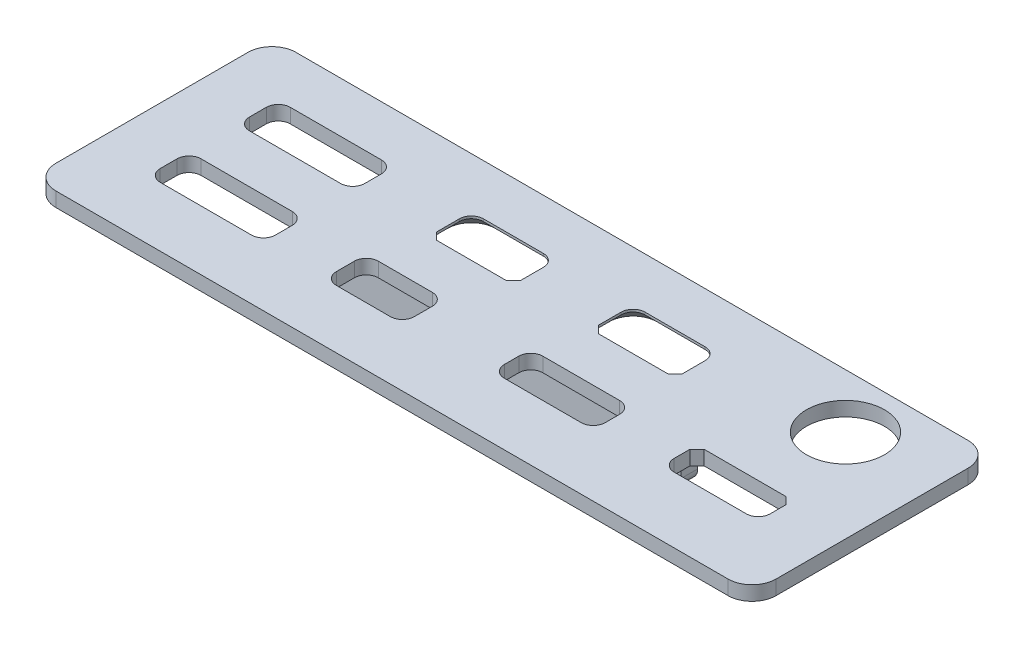
SolidWorks part; units mm, degrees
ref_plane "前视基准面" through (0, 0, 0) normal (0, 0, 1) x (1, 0, 0)
ref_plane "上视基准面" through (0, 0, 0) normal (0, 1, 0) x (1, 0, 0)
ref_plane "右视基准面" through (0, 0, 0) normal (1, 0, 0) x (0, 0, -1)
sketch "草图1" plane through (0, 0, 0) normal (0, 1, 0) x (1, 0, 0)
  line L1 (-30, 10) -> (30, 10)
  line L2 (-30, 10) -> (-30, -10)
  line L3 (-30, -10) -> (30, -10)
  line L4 (30, 10) -> (30, -10)
  line L5 (-30, 10) -> (30, -10) construction
  line L6 (-30, -10) -> (30, 10) construction
  point P0 (0, 0)
  dimension "D1" = 60
  dimension "D2" = 20
extrude "凸台-拉伸1" add sketch "草图1" along normal blind 1.2
fillet "圆角1" radius 2 4 edges at (30, 0.6, 10) (30, 0.6, -10) (-30, 0.6, 10) (-30, 0.6, -10)
sketch "草图4" plane through (0, 1.2, 0) normal (0, 1, 0) x (1, 0, 0)
  line L0 (-30, 8) -> (-30, -8) construction
  line L1 (-25.2717, 5.8) -> (-15.6717, 5.8)
  line L2 (-25.2717, 5.8) -> (-25.2717, 2.4)
  line L3 (-25.2717, 2.4) -> (-15.6717, 2.4)
  line L4 (-15.6717, 5.8) -> (-15.6717, 2.4)
  line L5 (-9.1829, 5.8) -> (-2.1829, 5.8)
  line L6 (-9.1829, 5.8) -> (-9.1829, 2.3)
  line L7 (-9.1829, 2.3) -> (-2.1829, 2.3)
  line L8 (-2.1829, 5.8) -> (-2.1829, 2.3)
  line L9 (4.2885, 5.8) -> (11.2885, 5.8)
  line L10 (4.2885, 5.8) -> (4.2885, 2.3)
  line L11 (4.2885, 2.3) -> (11.2885, 2.3)
  line L12 (11.2885, 5.8) -> (11.2885, 2.3)
  line L13 (17.05, -1.6348) -> (25.05, -1.6348)
  line L14 (17.05, -1.6348) -> (17.05, -4.5348)
  line L15 (17.05, -4.5348) -> (25.05, -4.5348)
  line L16 (25.05, -1.6348) -> (25.05, -4.5348)
  line L17 (3.2, -1.6348) -> (11.6, -1.6348)
  line L18 (3.2, -1.6348) -> (3.2, -4.8348)
  line L19 (3.2, -4.8348) -> (11.6, -4.8348)
  line L20 (11.6, -1.6348) -> (11.6, -4.8348)
  line L21 (-10.5, -1.6348) -> (-4, -1.6348)
  line L22 (-10.5, -1.6348) -> (-10.5, -5.1348)
  line L23 (-10.5, -5.1348) -> (-4, -5.1348)
  line L24 (-4, -1.6348) -> (-4, -5.1348)
  line L25 (-25.2717, -1.6348) -> (-15.6717, -1.6348)
  line L26 (-25.2717, -1.6348) -> (-25.2717, -5.0348)
  line L27 (-25.2717, -5.0348) -> (-15.6717, -5.0348)
  line L28 (-15.6717, -1.6348) -> (-15.6717, -5.0348)
  line L29 (28, 10) -> (-28, 10) construction
  line L30 (-28, -10) -> (28, -10) construction
  line L31 (30, -8) -> (30, 8) construction
  circle A0 centre (22.2985, 5.4832) radius 3.25
  dimension "D21" = 6.5
  dimension "D1" = 3.5
  dimension "D2" = 6.5
  dimension "D3" = 8.4
  dimension "D4" = 3.2
  dimension "D5" = 9.6
  dimension "D6" = 3.4
  dimension "D7" = 7
  dimension "D8" = 8
  dimension "D9" = 2.9
  dimension "D10" = 4.7283
  dimension "D11" = 7.6
  dimension "D12" = 4.9652
  dimension "D13" = 19.5
  dimension "D14" = 33.2
  dimension "D15" = 4.95
  dimension "D16" = 7
  dimension "D17" = 20.8171
  dimension "D18" = 34.2885
  dimension "D19" = 7.7015
  dimension "D20" = 4.5168
  dimension "D22" = 3.5
extrude "切除-拉伸1" cut sketch "草图4" against normal up to next
fillet "圆角2" radius 1 22 edges at (-25.2717, 0.6, -2.4) (-25.2717, 0.6, -5.8) (-15.6717, 0.6, -2.4) (-15.6717, 0.6, -5.8) (-2.1829, 0.6, -5.8) (-9.1829, 0.6, -5.8) (4.2885, 0.6, -5.8) (11.2885, 0.6, -5.8) (25.05, 0.6, 4.5348) (17.05, 0.6, 4.5348) (11.6, 0.6, 4.8348) (11.6, 0.6, 1.6348) (3.2, 0.6, 1.6348) (3.2, 0.6, 4.8348) (-4, 0.6, 5.1348) (-4, 0.6, 1.6348) (-10.5, 0.6, 1.6348) (-10.5, 0.6, 5.1348) (-15.6717, 0.6, 5.0348) (-15.6717, 0.6, 1.6348) (-25.2717, 0.6, 1.6348) (-25.2717, 0.6, 5.0348)
chamfer "倒角1" distance 0.6 angle 45 6 edges at (-9.1829, 0.6, -2.3) (-2.1829, 0.6, -2.3) (4.2885, 0.6, -2.3) (11.2885, 0.6, -2.3) (17.05, 0.6, 1.6348) (25.05, 0.6, 1.6348)
sketch "草图5" plane through (0, 0, 0) normal (0, -1, 0) x (1, 0, 0)
  line L0 (-30, -8) -> (-30, 8) construction
  line L1 (-13.9089, -4.8832) -> (-12.4089, -4.8832)
  line L2 (-13.9089, -4.8832) -> (-13.9089, 3.1168)
  line L3 (-13.9089, 3.1168) -> (-12.4089, 3.1168)
  line L4 (-12.4089, -4.8832) -> (-12.4089, 3.1168)
  line L5 (13.0911, -4.8832) -> (14.5911, -4.8832)
  line L6 (13.0911, -4.8832) -> (13.0911, 3.1168)
  line L7 (13.0911, 3.1168) -> (14.5911, 3.1168)
  line L8 (14.5911, -4.8832) -> (14.5911, 3.1168)
  line L9 (28, -10) -> (-28, -10) construction
  line L10 (30, 8) -> (30, -8) construction
  dimension "D1" = 1.5
  dimension "D2" = 8
  dimension "D3" = 1.5
  dimension "D4" = 8
  dimension "D5" = 16.0911
  dimension "D6" = 5.1168
  dimension "D7" = 5.1168
  dimension "D8" = 15.4089
extrude "凸台-拉伸2" add sketch "草图5" along normal blind 0.95
sketch "草图6" plane through (0, 0, 0) normal (0, -1, 0) x (1, 0, 0)
  line L0 (-13.9089, 3.1168) -> (-13.9089, -4.8832) construction
  line L1 (-13.9089, 0.5168) -> (14.5911, 0.5168)
  line L2 (-13.9089, 0.5168) -> (-13.9089, -0.8832)
  line L3 (-13.9089, -0.8832) -> (14.5911, -0.8832)
  line L4 (14.5911, 0.5168) -> (14.5911, -0.8832)
extrude "凸台-拉伸3" add sketch "草图6" along normal blind 4
fillet "圆角3" radius 1 2 edges at (14.5911, -4, -0.1832) (-13.9089, -4, -0.1832)
chamfer "倒角2" distance 1 angle 45 4 edges at (13.8411, -0.95, -4.8832) (-13.1589, -0.95, -4.8832) (13.8411, -0.95, 3.1168) (-13.1589, -0.95, 3.1168)
chamfer "倒角4" distance 1 angle 45 16 edges at (11.2885, 0, -3.85) (10.9956, 0, -5.5071) (7.7885, 0, -5.8) (4.5814, 0, -5.5071) (10.9885, 0, -2.6) (4.2885, 0, -3.85) (4.5885, 0, -2.6) (7.7885, 0, -2.3) (-9.1829, 0, -3.85) (-2.1829, 0, -3.85) (-8.89, 0, -5.5071) (-2.4758, 0, -5.5071) (-5.6829, 0, -5.8) (-2.4829, 0, -2.6) (-8.8829, 0, -2.6) (-5.6829, 0, -2.3)
